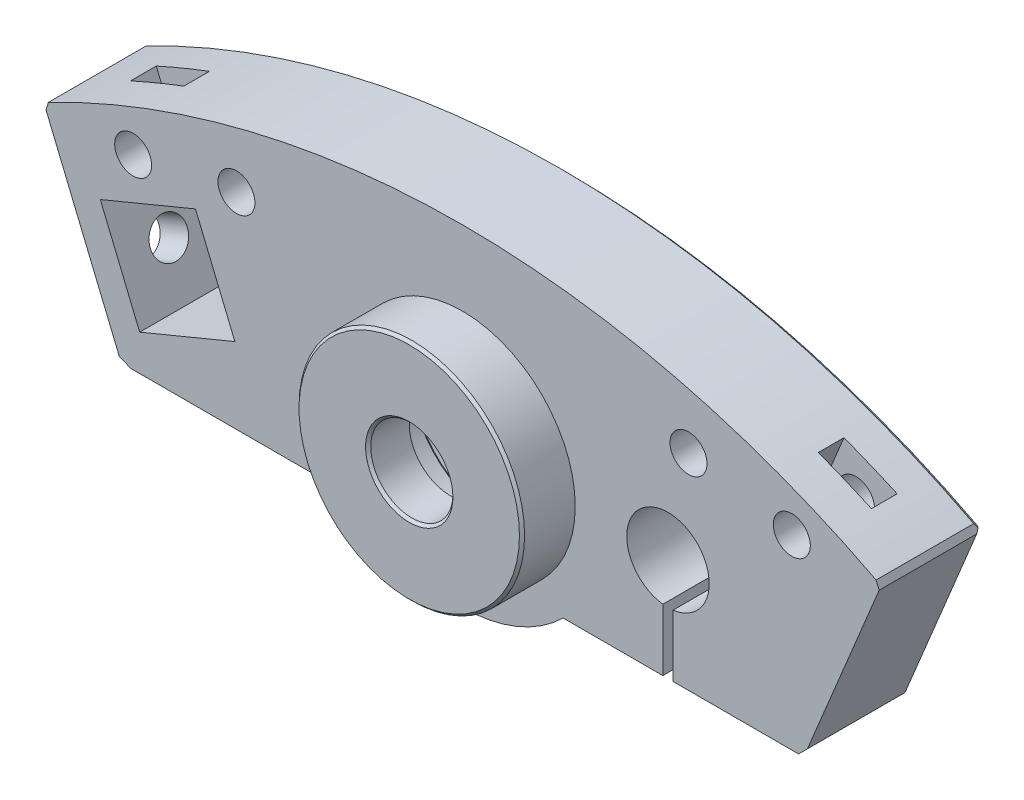
SolidWorks part; units mm, degrees
ref_plane "Front Plane" through (0, 0, 0) normal (0, 0, 1) x (1, 0, 0)
ref_plane "Top Plane" through (0, 0, 0) normal (0, 1, 0) x (1, 0, 0)
ref_plane "Right Plane" through (0, 0, 0) normal (1, 0, 0) x (0, 0, -1)
sketch "Sketch1" plane through (0, 0, 0) normal (0, 0, 1) x (1, 0, 0)
  line L0 (-46.9014, 0) -> (43.5211, 0) construction
  line L1 (0, 38.5211) -> (0, -80.4339) construction
  line L2 (-33.5349, -69.25) -> (36.7559, -69.25) construction
  line L3 (0, -69.25) -> (-37.9703, 22.4183) construction
  line L4 (-40.7467, 8.1836) -> (-33.2148, -10)
  line L5 (-25.9885, 6.5901) -> (-35.2504, 2.7537)
  line L6 (-35.2504, 2.7537) -> (-31.414, -6.5082)
  line L7 (-31.414, -6.5082) -> (-22.1521, -2.6718)
  line L8 (-22.1521, -2.6718) -> (-25.9885, 6.5901)
  line L9 (-33.2148, -10) -> (-9.798, -10)
  line L10 (33.2148, -10) -> (20.5, -10)
  line L11 (40.7467, 8.1836) -> (33.2148, -10)
  line L12 (20, 7.6703) -> (20, -11.9024) construction
  line L13 (19.5, -3.9812) -> (19.5, -10)
  line L14 (20.5, -3.9812) -> (20.5, -10)
  line L15 (19.5, -10) -> (9.798, -10)
  arc A0 (20.5, -3.9812) -> (19.5, -3.9812) centre (20, 0) ccw
  circle A1 centre (-28.7013, 0.041) radius 5.0125 construction
  arc A2 (40.7467, 8.1836) -> (-40.7467, 8.1836) centre (0, -69.25) ccw
  arc A5 (-9.798, -10) -> (9.798, -10) centre (0, 0) ccw
  circle A6 centre (0, 0) radius 5
  circle A7 centre (-32.0522, 8.1309) radius 1.8
  circle A8 centre (32.0522, 8.1309) radius 1.8
  circle A9 centre (-22, 10) radius 1.8
  circle A10 centre (22, 10) radius 1.8
  dimension "D1" = 20
  dimension "D2" = 8.025
  dimension "D7" = 75
  dimension "D8" = 175
  dimension "D9" = 3
  dimension "D10" = 14
  dimension "D12" = 10
  dimension "D13" = 3.6
  dimension "D15" = 3.6
  dimension "D16" = 22
  dimension "D17" = 79.25
  dimension "D3" = 69.25
  dimension "D4" = 22.5
  dimension "D5" = 10.025
  dimension "D6" = 90
  dimension "D11" = 10
  dimension "D14" = 0.5
extrude "Boss-Extrude1" add sketch "Sketch1" along normal blind 10
chamfer "Chamfer1" distance 0.5 5 edges at (-33.3322, -1.8772, 0) (-26.7831, -4.59, 0) (-24.0703, 1.9592, 0) (-30.6195, 4.6719, 0) (20, 4.0125, 0)
ref_plane "Plane1" through (0, 0, 3.75) normal (0, 0, 1) x (1, 0, 0)
sketch "Sketch3" plane through (0, 0, 3.75) normal (0, 0, 1) x (1, 0, 0)
  line L0 (-56.5816, 0) -> (49.5436, 0) construction
  line L1 (0, 34.2126) -> (0, -24.5915) construction
  line L2 (-26.7831, -4.59) -> (-35.1783, 15.678) construction
  line L3 (-31.414, -6.5082) -> (-22.1521, -2.6718) construction
  line L4 (-37.0768, 12.9445) -> (-33.5676, 4.4725)
  line L5 (-33.5676, 4.4725) -> (-28.3938, 6.6155)
  line L6 (-31.903, 15.0875) -> (-28.3938, 6.6155)
  line L7 (-37.0768, 12.9445) -> (-31.903, 15.0875)
  line L8 (37.0768, 12.9445) -> (33.5676, 4.4725)
  line L9 (33.5676, 4.4725) -> (28.3938, 6.6155)
  line L10 (31.903, 15.0875) -> (28.3938, 6.6155)
  line L11 (37.0768, 12.9445) -> (31.903, 15.0875)
  circle A0 centre (-32.0522, 8.1309) radius 1.8 construction
  point P15 (-30.9807, 5.544)
  dimension "D1" = 22.5
  dimension "D3" = 2.8
  dimension "D4" = 2.8
extrude "Cut-Extrude2" cut sketch "Sketch3" along normal blind 2.5
chamfer "Chamfer2" distance 0.5 angle 45 7 edges at (14.649, -10, 0) (0, -14, 0) (-21.5064, -10, 0) (-36.9808, -0.9082, 0) (26.8574, -10, 0) (36.9808, -0.9082, 0) (0, 18.25, 0)
sketch "Sketch4" plane through (-29.1145, -12.0596, 0) normal (0.9239, 0.3827, 0) x (0, 0, -1)
  line L0 (-11.0407, 11.0213) -> (-0.5, 11.0213) construction
  line L1 (-0.5, 6.0088) -> (-0.5, 16.0338) construction
  line L2 (-5.25, 6.0088) -> (-5.25, 12.0172) construction
  line L3 (-10, 6.0088) -> (-0.5, 6.0088) construction
  circle A0 centre (-5.25, 11.0213) radius 1.8
  dimension "D1" = 3.6
extrude "Cut-Extrude3" cut sketch "Sketch4" against normal blind 10
chamfer "Chamfer3" distance 0.5 angle 45 4 edges at (40.7467, 8.1836, 5.25) (33.2148, -10, 5.25) (-33.2148, -10, 5.25) (-40.7467, 8.1836, 5.25) first distance on face at (36.9808, -0.9082, 5.25) first distance on face at (26.8574, -10, 5.25) first distance on face at (-36.7927, -1.3623, 5.25) first distance on face at (0, 13.2168, 5.25)
sketch "Sketch7" plane through (0, 0, 10) normal (0, 0, 1) x (1, 0, 0)
  circle A0 centre (0, 0) radius 10.975
  circle A1 centre (0, 0) radius 4
  dimension "D1" = 21.95
  dimension "D2" = 8
extrude "Boss-Extrude2" add sketch "Sketch7" along normal blind 5.18
sketch "Sketch8" plane through (0, 0, 0) normal (0, 0, 1) x (1, 0, 0)
  circle A0 centre (0, 0) radius 8.5125
  dimension "D1" = 17.025
extrude "Cut-Extrude6" cut sketch "Sketch8" along normal blind 11.18
sketch "Sketch9" plane through (0, 0, 0) normal (0, 0, 1) x (1, 0, 0)
  circle A0 centre (0, 0) radius 9.5125
  dimension "D1" = 19.025
extrude "Cut-Extrude8" cut sketch "Sketch9" along normal blind 6.32
chamfer "Chamfer4" distance 0.25 angle 45 3 edges at (4, 0, 15.18) (10.975, 0, 15.18) (8.5125, 0, 6.32)
